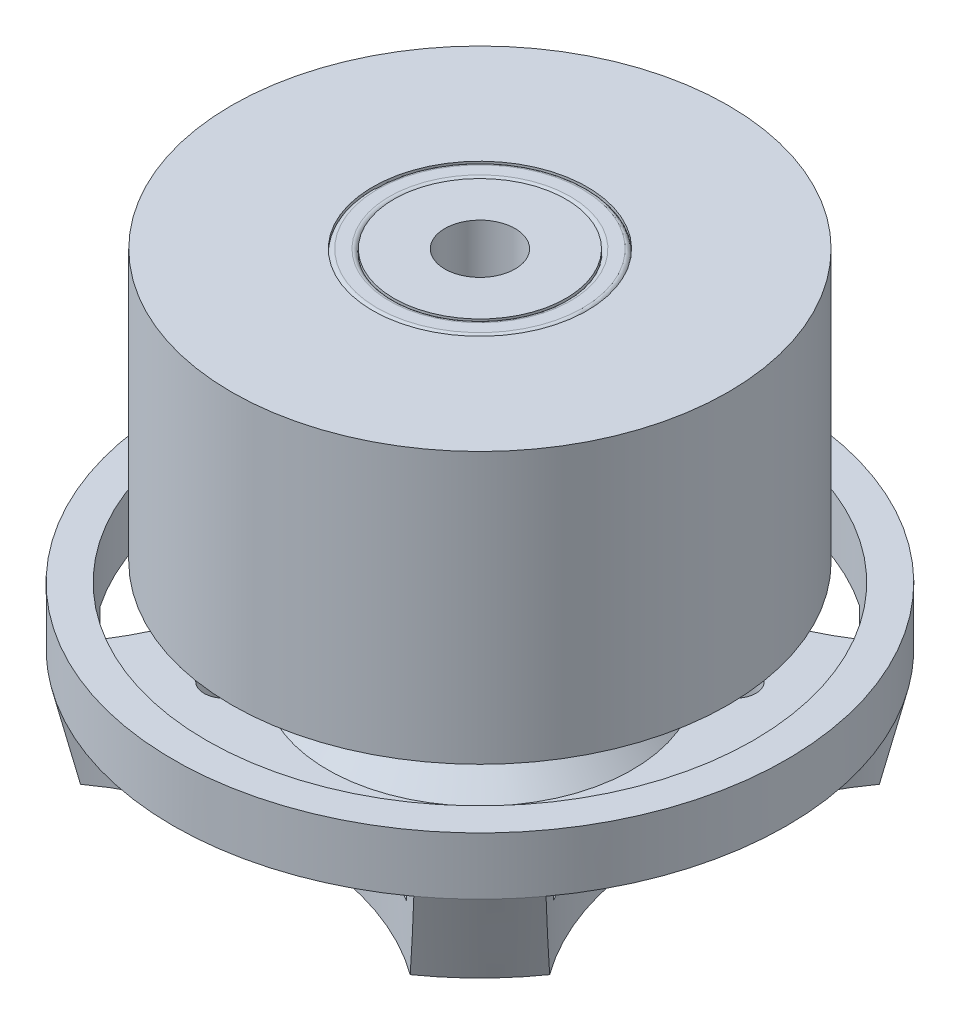
SolidWorks part; units mm, degrees
material "Plain Carbon Steel"
ref_plane "Front" through (0, 0, 0) normal (0, 0, 1) x (1, 0, 0)
ref_plane "Top" through (0, 0, 0) normal (0, 1, 0) x (1, 0, 0)
ref_plane "Right" through (0, 0, 0) normal (1, 0, 0) x (0, 0, -1)
sketch "Sketch1" plane through (0, 0, 0) normal (0, 0, 1) x (1, 0, 0)
  line L0 (0, 11.176) -> (1.5558, 11.176)
  line L1 (0, -50) -> (0, 50) construction
  line L2 (1.5558, 11.176) -> (1.5558, 0)
  line L3 (50, 0) -> (-50, 0) construction
  line L4 (1.5558, 0) -> (4.445, 0)
  line L5 (4.445, 0) -> (4.445, -1.524)
  line L6 (4.445, -1.524) -> (8.89, -1.524)
  line L7 (8.89, -1.524) -> (13.589, -5.08)
  line L8 (13.589, -5.08) -> (13.589, -5.842)
  line L9 (13.589, -5.842) -> (13.843, -5.842)
  line L10 (13.843, -5.842) -> (13.843, -20.4724)
  line L11 (13.589, -20.4724) -> (13.589, -23.0124)
  line L12 (13.589, -23.0124) -> (12.7, -26.67)
  line L13 (12.7, -26.67) -> (3.81, -26.67)
  line L14 (3.81, -26.67) -> (3.81, -26.924)
  line L15 (3.81, -26.924) -> (1.5558, -26.924)
  line L16 (1.5558, -26.924) -> (1.5558, -28.956)
  line L17 (1.5558, -28.956) -> (0, -28.956)
  line L18 (0, -28.956) -> (0, 11.176)
  line L19 (13.589, -20.4724) -> (13.843, -20.4724)
  dimension "D1" = 13.843
  dimension "D2" = 1.5557
  dimension "D3" = 11.176
  dimension "D4" = 4.445
  dimension "D5" = 1.524
  dimension "D6" = 8.89
  dimension "D7" = 4.318
  dimension "D8" = 0.762
  dimension "D9" = 0.254
  dimension "D10" = 14.6304
  dimension "D11" = 2.54
  dimension "D12" = 25.146
  dimension "D13" = 12.7
  dimension "D14" = 3.81
  dimension "D15" = 0.254
  dimension "D16" = 40.132
revolve "Revolve1" add sketch "Sketch1" angle 360 about L18
sketch "Sketch2" plane through (0, -1.524, 0) normal (0, 1, 0) x (1, 0, 0)
  circle A0 centre (0, 7.9375) radius 3.4925
  circle A1 centre (7.9375, 0) radius 3.4925
  circle A2 centre (0, -7.9375) radius 3.4925
  circle A3 centre (-7.9375, 0) radius 3.4925
  circle A5 centre (0, 0) radius 4.445 construction
  circle A7 centre (0, 0) radius 4.445 construction
  dimension "D2" = 6.985
extrude "Cut-Extrude1" cut sketch "Sketch2" against normal blind 5.08
sketch "Sketch3" plane through (0, -26.67, 0) normal (0, -1, 0) x (1, 0, 0)
  line L1 (-7.3025, 10.3905) -> (7.3025, 10.3905) construction
  circle A0 centre (0, 20.4866) radius 12.4602
  circle A1 centre (-20.4866, 0) radius 12.4602
  circle A2 centre (0, -20.4866) radius 12.4602
  circle A3 centre (20.4866, 0) radius 12.4602
  circle A4 centre (0, 0) radius 8.0264 construction
  circle A5 centre (0, 0) radius 12.7 construction
  dimension "D1" = 16.0528
  dimension "D2" = 14.605
extrude "Cut-Extrude2" cut sketch "Sketch3" against normal offset from surface (3.6576 mm away) 2.54 up to face at (0, -20.4724, -13.843)
sketch "Sketch4" plane through (0, -23.0124, 0) normal (0, -1, 0) x (1, 0, 0)
  circle A0 centre (0, 0) radius 12.1158
  arc A2 (8.0324, 10.9609) -> (-8.0324, 10.9609) centre (0, 0) ccw construction
  dimension "D1" = 1.4732
extrude "Cut-Extrude3" cut sketch "Sketch4" against normal blind 2.54 and the other way blind 1.27
hole_wizard "#4-40 Tapped Hole1" positions "Sketch7" profile "Sketch6" tap size "#4-40" standard "ANSI Inch"
sketch "Sketch7" plane through (0, -26.67, 0) normal (0, -1, 0) x (-1, 0, 0)
  line L0 (6.6723, 6.6723) -> (-6.6723, -6.6723) construction
  line L2 (5.6665, -5.6665) -> (-5.6665, 5.6665) construction
  line L5 (0, 0) -> (0, -19.5936) construction
  point P16 (5.6665, -5.6665)
  point P18 (-6.6723, -6.6723)
  point P20 (-5.6665, 5.6665)
  point P22 (6.6723, 6.6723)
  dimension "D1" = 18.8722
  dimension "D2" = 16.0274
  dimension "D3" = 45
sketch "Sketch6" plane through (-5.6665, -26.67, 5.6665) normal (1, 0, 0) x (0, 0, -1)
  line L0 (0, 0) -> (0, 3.0742)
  line L1 (0, 3.0742) -> (0.889, 2.54)
  line L2 (0.889, 2.54) -> (0.889, 0.6985)
  line L3 (0.889, 0.6985) -> (1.5875, 0)
  line L5 (1.5875, 0) -> (0, 0)
  line L6 (-0.889, 0.6985) -> (-1.5875, 0) construction
  line L10 (0, 3.0742) -> (-0.889, 2.54) construction
  line L11 (0, -6.35) -> (0, 107.95) construction
  dimension "Tap Drill Dia." = 1.778
  dimension "Tap Drill Depth" = 2.54
  dimension "Near C'Sink Dia." = 3.175
  dimension "Near C'Sink Angle" = 90
  dimension "Drill Angle" = 118
cosmetic thread "Hole Thread7" parameters "D1"=2.0853, "D2"=2.8448
cosmetic thread "Hole Thread8" parameters "D1"=2.0853, "D2"=2.8448
cosmetic thread "Hole Thread9" parameters "D1"=2.0853, "D2"=2.8448
cosmetic thread "Hole Thread10" parameters "D1"=2.0853, "D2"=2.8448
sketch "Sketch10" plane through (0, 0, 0) normal (1, 0, 0) x (0, 0, -1)
  line L1 (-12.1158, -20.4724) -> (12.1158, -20.4724) construction
  line L2 (-1.7272, -21.2979) -> (0, -21.2979) construction
  line L3 (0, -21.2979) -> (1.7272, -21.2979) construction
  circle A0 centre (0, -21.2979) radius 0.8255
  circle A1 centre (-1.7272, -21.2979) radius 0.8255
  circle A2 centre (1.7272, -21.2979) radius 0.8255
  dimension "D1" = 1.651
  dimension "D2" = 1.7272
sketch "Sketch12" plane through (0, 0, 0) normal (0, 0, 1) x (1, 0, 0)
  line L0 (0, -21.2979) -> (3.81, -21.2979)
  line L1 (0, -22.1234) -> (0, -20.4724) construction
  line L2 (9.5697, -23.8815) -> (51.689, -23.8815)
  line L3 (-13.843, -20.4724) -> (13.843, -20.4724) construction
  line L4 (-13.843, -20.4724) -> (13.589, -20.4724) construction
  line L5 (13.589, -23.0124) -> (13.589, -20.4724) construction
  arc A0 (3.81, -21.2979) -> (6.6898, -22.5897) centre (3.81, -25.1539) cw
  arc A1 (6.6898, -22.5897) -> (9.5697, -23.8815) centre (9.5697, -20.0255) ccw
  dimension "D1" = 2.5836
  dimension "D2" = 38.1
  dimension "D3" = 3.81
sketch "Sketch13" plane through (0, -20.4724, 0) normal (0, -1, 0) x (1, 0, 0)
  circle A0 centre (0, 0) radius 32.4311
extrude "Cut-Extrude5" cut sketch "Sketch13" against normal through all
sketch "Sketch14" plane through (0, -28.956, 0) normal (0, -1, 0) x (1, 0, 0)
  circle A1 centre (0, 0) radius 1.5558
  circle A2 centre (0, 0) radius 1.5558
  dimension "D1" = 0
extrude "Cut-Extrude6" cut sketch "Sketch14" against normal up to next
sketch "Sketch15" plane through (0, -24.2824, 0) normal (0, 1, 0) x (1, 0, 0)
  circle A0 centre (0, 0) radius 3.81 construction
  circle A1 centre (0, 0) radius 3.81
  circle A2 centre (0, 0) radius 4.75
  dimension "D1" = 9.5
extrude "Boss-Extrude1" add sketch "Sketch15" along normal blind 19 from surface at -2.3876 starting at face at (-5.6665, -26.67, 4.079)
chamfer "Chamfer1" distance 2 angle 45 1 edges at (0, -24.2824, -4.75)
sketch "Sketch16" plane through (0, -7.67, 0) normal (0, 1, 0) x (1, 0, 0)
  circle A0 centre (0, 0) radius 11
  circle A1 centre (0, 0) radius 4.75 construction
  circle A2 centre (0, 0) radius 4.75
  dimension "D1" = 22
extrude "Boss-Extrude2" add sketch "Sketch16" against normal blind 12 separate body
sketch "Sketch17" plane through (0, -7.67, 0) normal (0, 1, 0) x (1, 0, 0)
  circle A0 centre (0, 0) radius 1.5558 construction
  circle A1 centre (0, 0) radius 3.81 construction
  circle A2 centre (0, 0) radius 1.5558
  circle A3 centre (0, 0) radius 3.81
extrude "Boss-Extrude3" add sketch "Sketch17" against normal blind 3 separate body
fillet "Fillet1" radius 0.2 1 edges at (0, -7.67, -4.75)
fillet "Fillet2" radius 0.2 1 edges at (0, -7.67, -3.81)
ref_plane "Plane1" through (0, 0, 0) normal (-0.7071, 0, 0.7071) x (0.7071, 0, 0.7071)
